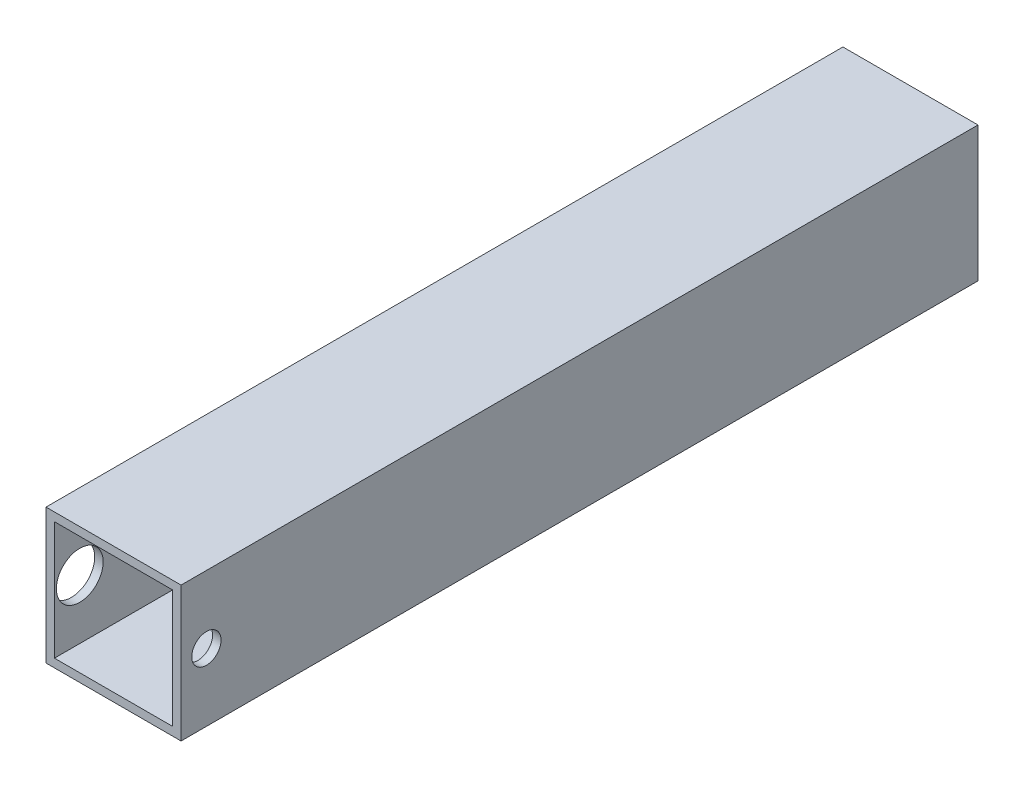
SolidWorks part; units mm, degrees
ref_plane "Front Plane" through (0, 0, 0) normal (0, 0, 1) x (1, 0, 0)
ref_plane "Top Plane" through (0, 0, 0) normal (0, 1, 0) x (1, 0, 0)
ref_plane "Right Plane" through (0, 0, 0) normal (1, 0, 0) x (0, 0, -1)
sketch "Sketch1" plane through (0, 0, 0) normal (0, 0, 1) x (1, 0, 0)
  line L1 (-12.7, -12.7) -> (12.7, -12.7)
  line L2 (-12.7, -12.7) -> (-12.7, 12.7)
  line L3 (-12.7, 12.7) -> (12.7, 12.7)
  line L4 (12.7, -12.7) -> (12.7, 12.7)
  line L5 (-12.7, -12.7) -> (12.7, 12.7) construction
  line L6 (-12.7, 12.7) -> (12.7, -12.7) construction
  point P0 (0, 0)
  dimension "D1" = 25.4
  dimension "D2" = 25.4
extrude "Boss-Extrude1" add sketch "Sketch1" along normal mid plane 149.86
shell "Shell1" thickness 1.5875 removed face at (0, 0, -74.93) removed face at (0, 0, 74.93)
hole_wizard "CBORE for M5 SHCS1" positions "Sketch3" profile "Sketch2" counterbore size "M5" standard "ANSI Metric" end condition through all
sketch "Sketch3" plane through (-12.7, 0, 0) normal (-1, 0, 0) x (0, 0, 1)
  line L2 (74.93, 12.7) -> (74.93, -12.7) construction
  point P0 (70.1675, 0)
  dimension "D1" = 4.7625
sketch "Sketch2" plane through (-12.7, 0, 70.1675) normal (0, 1, 0) x (0, 0, 1)
  line L0 (0, 0) -> (0, 25.4)
  line L1 (0, 25.4) -> (2.75, 25.4)
  line L3 (2.75, 25.4) -> (2.75, 5)
  line L4 (2.75, 5) -> (4.4, 5)
  line L5 (4.4, 5) -> (4.4, 0)
  line L7 (4.4, 0) -> (0, 0)
  line L11 (0, -6.35) -> (0, 107.95) construction
  dimension "Thru Hole Dia." = 5.5
  dimension "Thru Hole Depth" = 25.4
  dimension "C'Bore Dia." = 8.8
  dimension "C'Bore Depth" = 5
